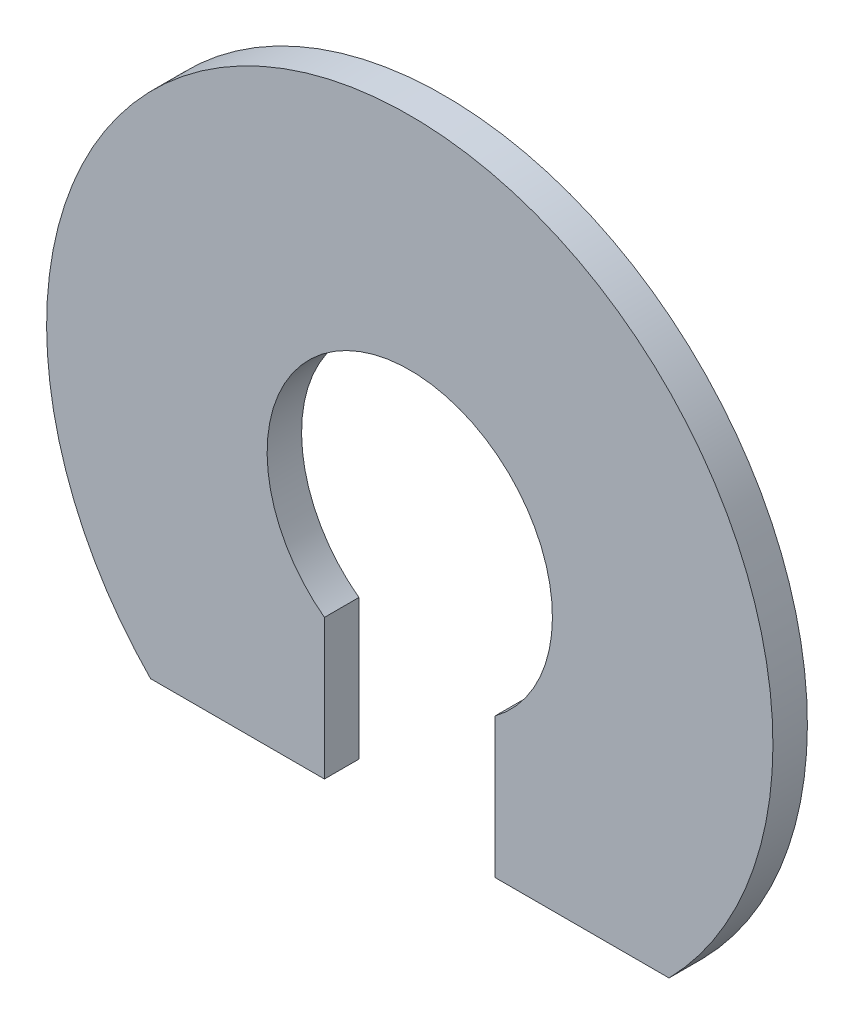
SolidWorks part; units mm, degrees
material "Alloy Steel"
ref_plane "Front Plane" through (0, 0, 0) normal (0, 0, 1) x (1, 0, 0)
ref_plane "Top Plane" through (0, 0, 0) normal (0, 1, 0) x (1, 0, 0)
ref_plane "Right Plane" through (0, 0, 0) normal (1, 0, 0) x (0, 0, -1)
sketch "Sketch1" plane through (0, 0, 0) normal (0, 0, 1) x (1, 0, 0)
  circle A0 centre (0, 0) radius 6.6929
  circle A1 centre (0, 0) radius 2.6289
extrude "Extrude1" add sketch "Sketch1" along normal blind 0.635
sketch "Sketch3" plane through (0, 0, 0.635) normal (0, 0, 1) x (1, 0, 0)
  line L0 (0, 0) -> (0, -4.6867) construction
  line L1 (0, -4.6867) -> (-4.778, -4.6867)
  line L2 (0, -4.6867) -> (4.778, -4.6867)
  circle A0 centre (0, 0) radius 6.6929 construction
  arc A1 (-4.778, -4.6867) -> (4.6867, -4.778) centre (0, 0) ccw
extrude "Extrude2" cut sketch "Sketch3" against normal through all and the other way through all flip side to cut
sketch "Sketch5" plane through (0, 0, 0.635) normal (0, 0, 1) x (1, 0, 0)
  line L0 (-1.5727, -0.5711) -> (-1.5727, -4.6867)
  line L1 (-1.5727, -0.5711) -> (1.5727, -0.5711)
  line L2 (-1.5727, -4.6867) -> (1.5727, -4.6867)
  line L3 (1.5727, -0.5711) -> (1.5727, -4.6867)
  line L4 (-1.5727, -0.5711) -> (1.5727, -4.6867) construction
  line L5 (-1.5727, -4.6867) -> (1.5727, -0.5711) construction
  circle A0 centre (0, 0) radius 2.6289 construction
  point P1 (0, -2.6289)
extrude "Extrude3" cut sketch "Sketch5" against normal blind 0.635
